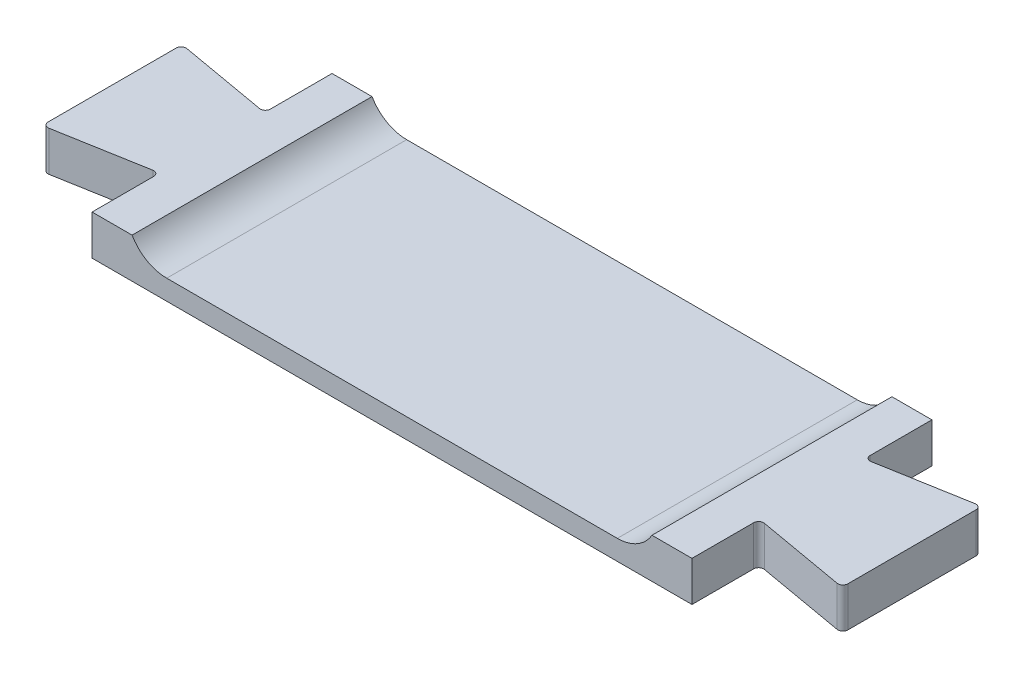
SolidWorks part; units mm, degrees
ref_plane "Front Plane" through (0, 0, 0) normal (0, 0, 1) x (1, 0, 0)
ref_plane "Top Plane" through (0, 0, 0) normal (0, 1, 0) x (1, 0, 0)
ref_plane "Right Plane" through (0, 0, 0) normal (1, 0, 0) x (0, 0, -1)
sketch "Sketch1" plane through (0, 0, 0) normal (0, 1, 0) x (1, 0, 0)
  line L0 (-15, 2.6184) -> (-20, 3.5)
  line L1 (-15, -6) -> (15, -6)
  line L2 (-15, -6) -> (-15, -2.6184)
  line L3 (-15, 6) -> (15, 6)
  line L4 (15, -6) -> (15, -2.6184)
  line L5 (-15, -6) -> (15, 6) construction
  line L6 (-15, 6) -> (15, -6) construction
  line L7 (-20, 3.5) -> (-20, -3.5)
  line L8 (-10, 0) -> (-18.3718, 0) construction
  line L9 (-15, -2.6184) -> (-20, -3.5)
  line L10 (-15, 2.6184) -> (-15, 6)
  line L11 (0, 0) -> (0, 6) construction
  line L12 (15, -2.6184) -> (20, -3.5)
  line L13 (20, 3.5) -> (20, -3.5)
  line L14 (15, 2.6184) -> (20, 3.5)
  line L15 (15, 2.6184) -> (15, 6)
  line L16 (-15, 6) -> (-25.4194, 6) construction
  point P0 (0, 0)
  point P13 (-20, 0)
  dimension "D1" = 12
  dimension "D2" = 30
  dimension "D3" = 3.5
  dimension "D4" = 80
  dimension "D5" = 5
extrude "Boss-Extrude1" add sketch "Sketch1" along normal blind 2
fillet "Fillet1" radius 0.25 8 edges at (-15, 1, 2.6184) (-20, 1, 3.5) (-20, 1, -3.5) (-15, 1, -2.6184) (15, 1, -2.6184) (20, 1, -3.5) (20, 1, 3.5) (15, 1, 2.6184)
shell "Shell1" [suppressed] thickness 1
fillet "Fillet2" [suppressed] radius 0.5
fillet "Fillet5" [suppressed] radius 1.5
sketch "Sketch2" plane through (0, 0, 0) normal (0, 0, 1) x (1, 0, 0)
  line L0 (-15, 2) -> (15, 2) construction
  line L1 (0, 0) -> (0, 2) construction
  line L2 (-14.5, 2) -> (-14.5, 5.1779)
  line L3 (-15, 0) -> (15, 0) construction
  line L4 (-14.5, 5.1779) -> (14.5, 5.1779)
  line L5 (14.5, 2) -> (14.5, 5.1779)
  spline S0 degree 3 poles (-14.5, 2) (-10.1117, 3.708) (-5.6899, 1.0248) (0, 1) knots 0 0 0 0 1 1 1 1
  spline S1 degree 3 poles (14.5, 2) (10.1117, 3.708) (5.6899, 1.0248) (0, 1) knots 0 0 0 0 1 1 1 1
  point P15 (0, 5.1779)
  dimension "D1" = 14.5
  dimension "D2" = 10
  dimension "D3" = 1
extrude "Cut-Extrude1" [suppressed] cut sketch "Sketch2" against normal mid plane 12
sketch "Sketch3" plane through (0, 2, 0) normal (0, 1, 0) x (1, 0, 0)
  line L0 (15, 6) -> (-15, 6) construction
  line L1 (-13, 6) -> (13, 6)
  line L2 (-13, 6) -> (-13, -6)
  line L3 (-13, -6) -> (13, -6)
  line L4 (13, 6) -> (13, -6)
  line L5 (-15, -6) -> (15, -6) construction
  line L6 (-15, 6) -> (-15, 2.9163) construction
  line L7 (15, 2.9163) -> (15, 6) construction
  point P8 (-15, 4.4582)
  point P11 (15, 4.4582)
  dimension "D1" = 2
  dimension "D2" = 2
extrude "Cut-Extrude2" cut sketch "Sketch3" against normal blind 1
fillet "Fillet6" radius 2 2 edges at (-13, 1, 0) (13, 1, 0)
